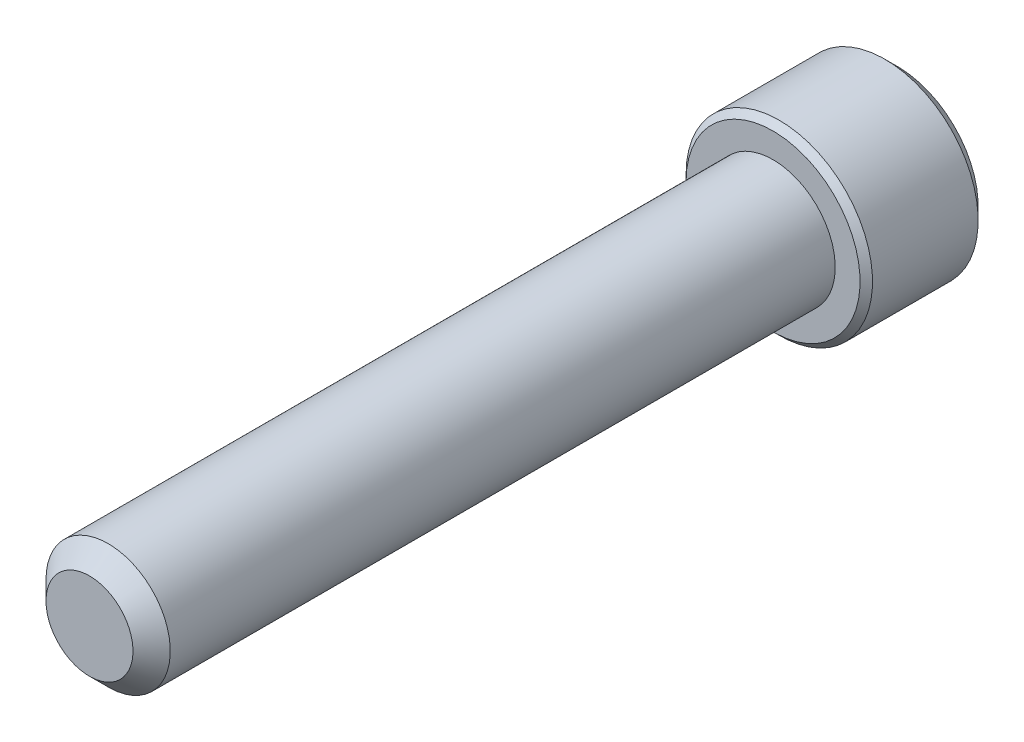
SolidWorks part; units mm, degrees
material "Wrought Stainless Steel"
ref_plane "Front Plane" through (0, 0, 0) normal (0, 0, 1) x (1, 0, 0)
ref_plane "Top Plane" through (0, 0, 0) normal (0, 1, 0) x (1, 0, 0)
ref_plane "Right Plane" through (0, 0, 0) normal (1, 0, 0) x (0, 0, -1)
sketch "Sketch1" plane through (0, 0, 0) normal (0, 0, 1) x (1, 0, 0)
  line L0 (0, 3.175) -> (0, -3.175) construction
  circle A0 centre (0, 0) radius 3.175
  dimension "OD" = 6.35
extrude "Extrude1" add sketch "Sketch1" against normal blind 34.925
sketch "Sketch2" plane through (0, 0, 0) normal (0, 0, 1) x (1, 0, 0)
  circle A0 centre (0, 0) radius 3.175 construction
  circle A1 centre (0, 0) radius 3.175
curve "Helix/Spiral1" pitch 1.27 height 36.195 turns 28.5 parameters "pitch"=1.27
chamfer "Chamfer3" distance 0.9525 angle 45 1 edges at (3.175, 0, 0)
sketch "Sketch3" plane through (0, 0, 0) normal (1, 0, 0) x (0, 0, -1)
  line L0 (-1.1113, 3.175) -> (-0.635, 2.3501)
  line L1 (-0.635, 2.3501) -> (-0.4763, 2.3501)
  line L2 (-0.4763, 2.3501) -> (0, 3.175)
  line L3 (-1.1113, 3.175) -> (0, 3.175)
  line L4 (-0.5556, 3.175) -> (-0.5556, 2.3501) construction
  line L5 (-0.8731, 2.7626) -> (-0.2381, 2.7626) construction
  line L6 (0, 3.175) -> (0, -3.175) construction
  dimension "D1" = 0.1588
  dimension "D2" = 0.635
  dimension "D3" = 60
sweep "Cut-Sweep1" [suppressed] cut profiles "Sketch3" path "Helix/Spiral1"
sketch "Sketch6" plane through (0, 0, -34.925) normal (0, 0, -1) x (-1, 0, 0)
  circle A0 centre (0, 0) radius 4.7625
  dimension "head dia" = 9.525
extrude "Extrude2" add sketch "Sketch6" along normal blind 6.35
sketch "Sketch7" plane through (0, 0, -41.275) normal (0, 0, -1) x (-1, 0, 0)
  line L1 (0, 2.7496) -> (-2.3813, 1.3748)
  line L2 (-2.3813, 1.3748) -> (-2.3813, -1.3748)
  line L3 (-2.3813, -1.3748) -> (0, -2.7496)
  line L4 (0, -2.7496) -> (2.3813, -1.3748)
  line L5 (2.3813, -1.3748) -> (2.3813, 1.3748)
  line L6 (2.3813, 1.3748) -> (0, 2.7496)
  circle A0 centre (0, 0) radius 2.3813 construction
  dimension "hex dia" = 4.7625
extrude "Cut-Extrude1" cut sketch "Sketch7" against normal blind 3.5719
sketch "Sketch8" plane through (0, 0, -41.275) normal (0, 0, -1) x (-1, 0, 0)
  circle A0 centre (0, 0) radius 2.7496
extrude "Cut-Extrude2" cut sketch "Sketch8" against normal blind 0.635 draft 45
chamfer "Chamfer1" distance 0.635 angle 45 1 edges at (-4.7625, 0, -41.275)
chamfer "Chamfer2" distance 0.3175 angle 45 1 edges at (-4.7625, 0, -34.925)
sketch "Sketch9" plane through (0, 0, 0) normal (1, 0, 0) x (0, 0, -1)
  line L0 (0, 3.175) -> (0, -3.175) construction
  line L1 (6.985, 3.175) -> (6.985, -3.175) construction
  line L2 (34.925, 4.7625) -> (34.925, -4.7625) construction
  line L3 (41.275, 4.7625) -> (41.275, -4.7625) construction
  line L4 (41.275, 0) -> (0, 0) construction
  dimension "D1" = 6.985
  dimension "D2" = 6.35
  dimension "D3" = 9.525
  dimension "D4" = 34.925
equation "\"D3@Helix/Spiral1\" = \"screw length@Extrude1\"+\"pitch@Helix/Spiral1\""
equation "\"D1@Sketch3\" = \"pitch@Helix/Spiral1\"*.125"
equation "\"D2@Sketch3\" = \"pitch@Helix/Spiral1\"*.5"
equation "\"D1@Cut-Extrude1\" = \"hex dia@Sketch7\"*.75"
equation "\"D1@Chamfer1\" = \"head depth@Extrude2\"/10"
equation "\"D1@Sketch9\" = \"pitch@Helix/Spiral1\"*5.5"
equation "\"D1@Chamfer2\" = \"D1@Chamfer1\"/2"
equation "\"D1@Cut-Extrude2\" = \"D1@Chamfer2\"*2"
equation "\"D1@Chamfer3\" = \"pitch@Helix/Spiral1\"*.750"
equation "\"D2@Sketch9\" = \"head depth@Extrude2\""
equation "\"D3@Sketch9\" = \"head dia@Sketch6\""
equation "\"D4@Sketch9\" = \"screw length@Extrude1\""
